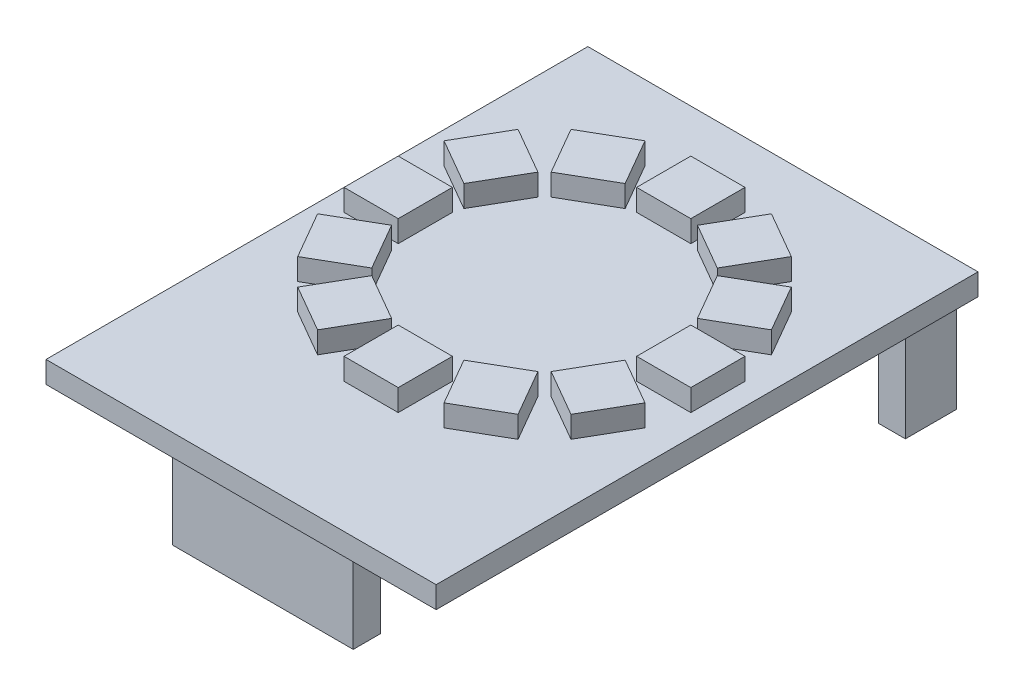
SolidWorks part; units mm, degrees
ref_plane "Front Plane" through (0, 0, 0) normal (0, 0, 1) x (1, 0, 0)
ref_plane "Top Plane" through (0, 0, 0) normal (0, 1, 0) x (1, 0, 0)
ref_plane "Right Plane" through (0, 0, 0) normal (1, 0, 0) x (0, 0, -1)
sketch "Sketch1" plane through (0, 0, 0) normal (0, 1, 0) x (1, 0, 0)
  line L1 (-18, -28) -> (18, -28)
  line L2 (-18, -28) -> (-18, 22)
  line L3 (-18, 22) -> (18, 22)
  line L4 (18, -28) -> (18, 22)
  point P4 (0, 22)
  dimension "D1" = 36
  dimension "D2" = 50
  dimension "D3" = 22
extrude "Boss-Extrude1" add sketch "Sketch1" along normal blind 2
sketch "Sketch2" plane through (0, 2, 0) normal (0, 1, 0) x (1, 0, 0)
  line L1 (-2.5, 16) -> (2.5, 16)
  line L2 (-2.5, 16) -> (-2.5, 11)
  line L3 (-2.5, 11) -> (2.5, 11)
  line L4 (2.5, 16) -> (2.5, 11)
  circle A0 centre (0, 0) radius 16 construction
  point P7 (0, 11)
  dimension "D1" = 32
  dimension "D2" = 5
  dimension "D3" = 5
extrude "Boss-Extrude2" add sketch "Sketch2" along normal blind 2
ref_axis "Axis1" through (0, 0, 0) along (0, 1, 0)
pattern_circular "CirPattern1" count 12 over 360 about axis through (0, 0, 0) along (0, 1, 0) of "Boss-Extrude2"
sketch "Sketch3" plane through (0, 0, 0) normal (0, -1, 0) x (1, 0, 0)
  line L0 (-18, 28) -> (18, 28) construction
  line L1 (-8.35, 26) -> (8.35, 26)
  line L2 (-8.35, 26) -> (-8.35, 23.5)
  line L3 (-8.35, 23.5) -> (8.35, 23.5)
  line L4 (8.35, 26) -> (8.35, 23.5)
  line L5 (-14.5, -16.3) -> (14.5, -16.3) construction
  line L6 (-17, -21) -> (-14.5, -21)
  line L7 (-17, -21) -> (-17, -16.3)
  line L8 (-17, -16.3) -> (-14.5, -16.3)
  line L9 (-14.5, -21) -> (-14.5, -16.3)
  line L10 (17, -21) -> (14.5, -21)
  line L11 (17, -21) -> (17, -16.3)
  line L12 (17, -16.3) -> (14.5, -16.3)
  line L13 (14.5, -21) -> (14.5, -16.3)
  line L14 (-18, -22) -> (-18, 28) construction
  line L15 (18, -22) -> (-18, -22) construction
  point P6 (0, 28)
  point P7 (0, 26)
  point P16 (0, -16.3)
  point P17 (-16.4311, -20.1224)
  dimension "D1" = 2.5
  dimension "D2" = 16.7
  dimension "D3" = 2
  dimension "D4" = 4.7
  dimension "D5" = 1
  dimension "D6" = 1
extrude "Boss-Extrude3" add sketch "Sketch3" along normal blind 9
